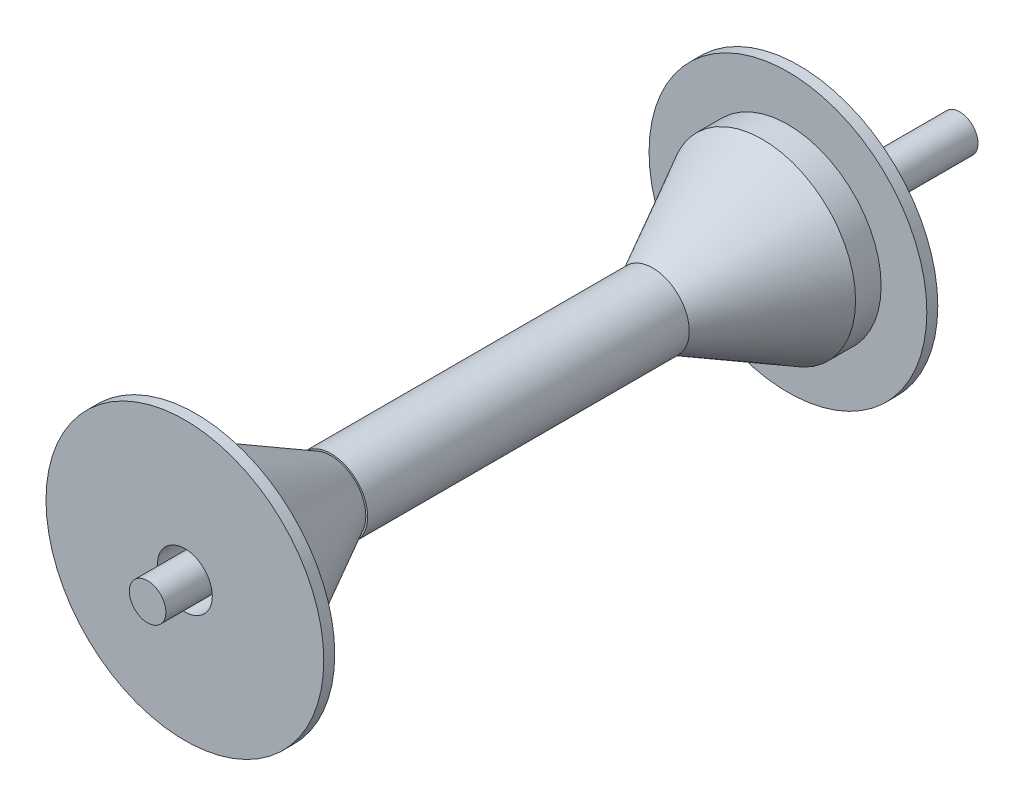
SolidWorks part; units mm, degrees
ref_plane "Front Plane" through (0, 0, 0) normal (0, 0, 1) x (1, 0, 0)
ref_plane "Top Plane" through (0, 0, 0) normal (0, 1, 0) x (1, 0, 0)
ref_plane "Right Plane" through (0, 0, 0) normal (1, 0, 0) x (0, 0, -1)
sketch "Sketch1" plane through (0, 0, 0) normal (0, 0, 1) x (1, 0, 0)
  circle A0 centre (0, 0) radius 6.35
  dimension "D1" = 12.7
extrude "Boss-Extrude1" add sketch "Sketch1" along normal blind 282.194
ref_plane "Plane1" through (0, 0, 5.08) normal (0, 0, -1) x (-1, 0, 0)
sketch "Sketch3" plane through (0, 0, 5.08) normal (0, 0, -1) x (-1, 0, 0)
  circle A0 centre (0, 0) radius 30.48
  dimension "D1" = 60.96
ref_plane "Plane2" through (0, 0, 55.88) normal (0, 0, -1) x (-1, 0, 0)
sketch "Sketch4" plane through (0, 0, 55.88) normal (0, 0, -1) x (-1, 0, 0)
  circle A0 centre (0, 0) radius 9.525
  dimension "D1" = 19.05
ref_plane "Plane3" through (0, 0, 141.097) normal (0, 0, 1) x (1, 0, 0)
ref_axis "Axis1" through (0, 0, 282.194) along (0, 0, -1)
sketch "Sketch8" plane through (0, 0, 55.88) normal (0, 0, -1) x (-1, 0, 0)
  circle A0 centre (0, 0) radius 12.7
  dimension "D1" = 25.4
sketch "Sketch11" plane through (0, 0, 55.88) normal (0, 0, -1) x (-1, 0, 0)
  circle A0 centre (0, 0) radius 30.48
  dimension "D1" = 60.96
ref_plane "Plane4" through (0, 0, 106.68) normal (0, 0, -1) x (-1, 0, 0)
sketch "Sketch12" plane through (0, 0, 106.68) normal (0, 0, -1) x (-1, 0, 0)
  circle A0 centre (0, 0) radius 9.525
  dimension "D1" = 19.05
sketch "Sketch14" plane through (0, 0, 0) normal (1, 0, 0) x (0, 0, -1)
  line L0 (-106.68, -6.985) -> (-106.68, 6.985) construction
  line L1 (-55.88, -30.48) -> (-55.88, 30.48) construction
  line L2 (-106.68, 9.525) -> (-55.88, 9.525)
  line L3 (-106.68, -9.525) -> (-106.68, 9.525) construction
  line L4 (-55.88, -9.525) -> (-55.88, 9.525) construction
  line L5 (-55.88, 9.525) -> (-55.88, 32.385)
  line L6 (-106.68, 12.065) -> (-106.68, 9.525)
  line L7 (-106.68, 9.525) -> (-55.88, 9.525) construction
  line L8 (-282.194, 0) -> (0, 0) construction
  line L10 (-55.88, 32.385) -> (-68.58, 32.385)
  line L11 (-68.58, 32.385) -> (-106.68, 12.065)
  dimension "D1" = 12.7
  dimension "D2" = 22.86
  dimension "D3" = 9.525
  dimension "D4" = 2.54
revolve "Revolve1" add sketch "Sketch14" angle 360 about axis through (0, 0, 282.194) along (0, 0, -1) other way angle 360
ref_plane "Plane5" through (0, 0, 162.56) normal (0, 0, -1) x (-1, 0, 0)
sketch "Sketch15" plane through (0, 0, 0) normal (1, 0, 0) x (0, 0, -1)
  line L0 (-55.88, -30.48) -> (-55.88, 30.48) construction
  line L1 (-55.88, 22.86) -> (-59.69, 22.86)
  line L2 (-55.88, 22.86) -> (-55.88, 48.26)
  line L3 (-55.88, 48.26) -> (-59.69, 48.26)
  line L4 (-59.69, 22.86) -> (-59.69, 48.26)
  line L5 (-282.194, 0) -> (0, 0) construction
  dimension "D1" = 25.4
  dimension "D2" = 3.81
  dimension "D3" = 22.86
revolve "Revolve2" add sketch "Sketch15" angle 360 about axis through (0, 0, 282.194) along (0, 0, -1) region at (0, 35.56, 57.785)
sketch "Sketch16" plane through (0, 0, 0) normal (0, 1, 0) x (1, 0, 0)
  line L0 (0, -282.194) -> (0, 0) construction
  line L1 (35.6235, -162.56) -> (-35.6235, -162.56) construction
  circle A0 centre (0, -88.9) radius 2.54
  circle A1 centre (0, -162.56) radius 2.54
  circle A2 centre (0, -236.22) radius 2.54
  dimension "D1" = 5.08
  dimension "D2" = 5.08
  dimension "D3" = 5.08
  dimension "D4" = 73.66
  dimension "D5" = 73.66
extrude "Cut-Extrude1" cut sketch "Sketch16" against normal through all both and the other way through all
combine bodies "Combine1" operation type add bodies to combine 127 126
mirror "Mirror4" about plane through (0, 0, 162.56) normal (0, 0, -1) of bodies 147
sketch "Sketch18" plane through (0, 0, 0) normal (0, 1, 0) x (1, 0, 0)
  line L0 (0, -106.68) -> (-12.7, -106.68) construction
  line L1 (9.525, -106.68) -> (-9.525, -106.68) construction
  line L2 (-12.7, -106.68) -> (-9.525, -106.68)
  line L3 (-12.7, -106.68) -> (-12.7, -218.44)
  line L4 (12.065, -218.44) -> (-12.065, -218.44) construction
  line L5 (-12.7, -218.44) -> (-9.525, -218.44)
  line L6 (9.525, -218.44) -> (-9.525, -218.44) construction
  line L7 (-9.525, -218.44) -> (-9.525, -106.68)
  dimension "D1" = 12.7
  dimension "D2" = 3.175
revolve "Revolve4" add sketch "Sketch18" angle 360 about axis through (0, 0, 282.194) along (0, 0, -1)
equation "\"A\"=0.5"
equation "\"D1@Sketch1\"=\"A\""
equation "\"B\"=0.2"
equation "\"D1@Sketch16\"=\"B\""
